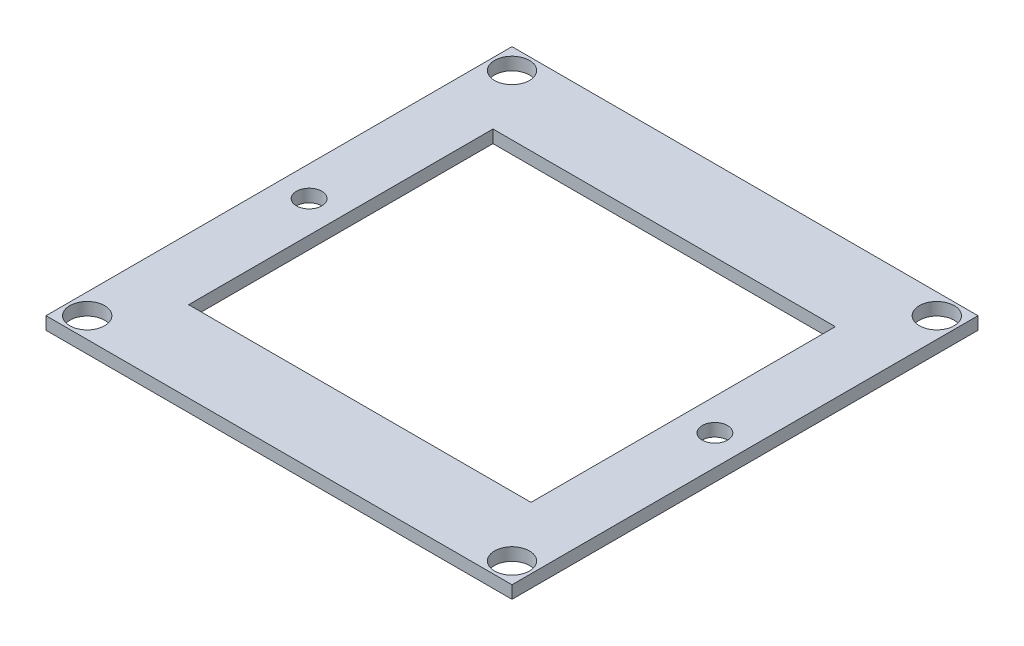
SolidWorks part; units mm, degrees
ref_plane "Front Plane" through (0, 0, 0) normal (0, 0, 1) x (1, 0, 0)
ref_plane "Top Plane" through (0, 0, 0) normal (0, 1, 0) x (1, 0, 0)
ref_plane "Right Plane" through (0, 0, 0) normal (1, 0, 0) x (0, 0, -1)
sketch "Sketch1" plane through (0, 0, 0) normal (0, 1, 0) x (1, 0, 0)
  line L0 (147, 147) -> (147, -147)
  line L1 (-147, -147) -> (147, -147)
  line L2 (-147, -147) -> (-147, 147)
  line L3 (-147, 147) -> (147, 147)
  line L5 (-147, -147) -> (147, 147) construction
  line L6 (-147, 147) -> (147, -147) construction
  line L7 (-108, -96) -> (108, -96)
  line L8 (-108, -96) -> (-108, 96)
  line L9 (-108, 96) -> (108, 96)
  line L10 (108, -96) -> (108, 96)
  line L11 (-108, -96) -> (108, 96) construction
  line L12 (-108, 96) -> (108, -96) construction
  point P0 (0, 0)
  point P5 (0, 0)
  dimension "D1" = 294
  dimension "D2" = 216
  dimension "D3" = 192
extrude "Boss-Extrude1" add sketch "Sketch1" along normal blind 8
sketch "Sketch2" plane through (0, 0, 0) normal (0, 1, 0) x (1, 0, 0)
  line L1 (147, 147) -> (-147, 147) construction
  line L2 (147, -147) -> (147, 147) construction
  circle A0 centre (134, 134) radius 11
  dimension "D1" = 22
  dimension "D2" = 13
  dimension "D3" = 13
extrude "Cut-Extrude1" cut sketch "Sketch2" along normal through all
sketch "Sketch4" plane through (0, 8, 0) normal (0, 1, 0) x (1, 0, 0)
  line L0 (134, -864) -> (134, 49136) construction
  circle A0 centre (128, 0) radius 8
  dimension "D1" = 6
  dimension "D2" = 16
mirror "Mirror2" about plane through (0, 0, 0) normal (0, 0, 1) of "Cut-Extrude1"
extrude "Cut-Extrude2" cut sketch "Sketch4" against normal through all
mirror "Mirror3" about plane through (0, 0, 0) normal (1, 0, 0) of "Mirror2", "Cut-Extrude1"
mirror "Mirror4" about plane through (0, 0, 0) normal (1, 0, 0) of "Cut-Extrude2"
